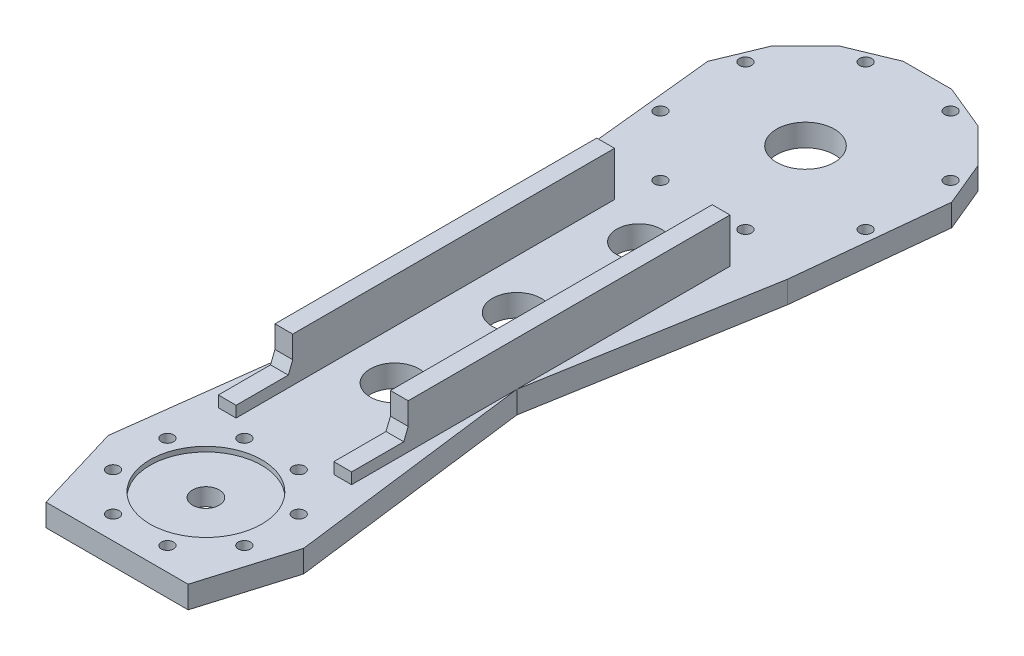
SolidWorks part; units mm, degrees
material "6061-T6 (SS)"
ref_plane "Front Plane" through (0, 0, 0) normal (0, 0, 1) x (1, 0, 0)
ref_plane "Top Plane" through (0, 0, 0) normal (0, 1, 0) x (1, 0, 0)
ref_plane "Right Plane" through (0, 0, 0) normal (1, 0, 0) x (0, 0, -1)
ref_plane "PL_Thigh_Plate_base" through (0, -46, 0) normal (0, 1, 0) x (1, 0, 0)
sketch "SK_Thigh_Plate" plane through (0, -46, 0) normal (0, 1, 0) x (1, 0, 0)
  line L0 (-32, -40) -> (32, -40)
  line L1 (32, -40) -> (44, 0)
  line L2 (44, 0) -> (30, 110)
  line L3 (30, 110) -> (48, 214)
  line L4 (48, 214) -> (54.924, 280.9251)
  line L5 (54.924, 280.9251) -> (46.5623, 301.1119)
  line L6 (46.5623, 301.1119) -> (31.1119, 316.5623)
  line L7 (31.1119, 316.5623) -> (10.9251, 324.924)
  line L8 (10.9251, 324.924) -> (-10.9251, 324.924)
  line L9 (-10.9251, 324.924) -> (-31.1119, 316.5623)
  line L10 (-31.1119, 316.5623) -> (-46.5623, 301.1119)
  line L11 (-46.5623, 301.1119) -> (-54.924, 280.9251)
  line L12 (-54.924, 280.9251) -> (-48, 214)
  line L13 (-48, 214) -> (-30, 110)
  line L14 (-30, 110) -> (-44, 0)
  line L15 (-44, 0) -> (-32, -40)
  circle A0 centre (29.5641, 12.2459) radius 2.75
  circle A1 centre (12.2459, 29.5641) radius 2.75
  circle A2 centre (-12.2459, 29.5641) radius 2.75
  circle A3 centre (-29.5641, 12.2459) radius 2.75
  circle A4 centre (-29.5641, -12.2459) radius 2.75
  circle A5 centre (-12.2459, -29.5641) radius 2.75
  circle A6 centre (12.2459, -29.5641) radius 2.75
  circle A7 centre (29.5641, -12.2459) radius 2.75
  circle A8 centre (46.194, 289.1342) radius 2.75
  circle A9 centre (19.1342, 316.194) radius 2.75
  circle A10 centre (-19.1342, 316.194) radius 2.75
  circle A11 centre (-46.194, 289.1342) radius 2.75
  circle A12 centre (-46.194, 250.8658) radius 2.75
  circle A13 centre (-19.1342, 223.806) radius 2.75
  circle A14 centre (19.1342, 223.806) radius 2.75
  circle A15 centre (46.194, 250.8658) radius 2.75
  circle A16 centre (0, 0) radius 6
  circle A17 centre (0, 270) radius 13
  circle A18 centre (0, 85) radius 11
  circle A19 centre (0, 140) radius 11
  circle A20 centre (0, 195) radius 10
  dimension "D31_SK_Thigh_Plate" = 5.5
  dimension "D34_SK_Thigh_Plate" = 5.5
  dimension "D37_SK_Thigh_Plate" = 5.5
  dimension "D40_SK_Thigh_Plate" = 5.5
  dimension "D43_SK_Thigh_Plate" = 5.5
  dimension "D46_SK_Thigh_Plate" = 5.5
  dimension "D49_SK_Thigh_Plate" = 5.5
  dimension "D52_SK_Thigh_Plate" = 5.5
  dimension "D55_SK_Thigh_Plate" = 5.5
  dimension "D58_SK_Thigh_Plate" = 5.5
  dimension "D61_SK_Thigh_Plate" = 5.5
  dimension "D64_SK_Thigh_Plate" = 5.5
  dimension "D67_SK_Thigh_Plate" = 5.5
  dimension "D70_SK_Thigh_Plate" = 5.5
  dimension "D73_SK_Thigh_Plate" = 5.5
  dimension "D76_SK_Thigh_Plate" = 5.5
  dimension "D79_SK_Thigh_Plate" = 12
  dimension "D80_SK_Thigh_Plate" = 26
  dimension "D82_SK_Thigh_Plate" = 22
  dimension "D84_SK_Thigh_Plate" = 22
  dimension "D86_SK_Thigh_Plate" = 20
  dimension "P1" = 32
  dimension "P2" = 40
  dimension "P3" = 32
  dimension "P4" = 40
  dimension "P5" = 44
  dimension "P6" = 30
  dimension "P7" = 110
  dimension "P8" = 48
  dimension "P9" = 214
  dimension "P10" = 54.924
  dimension "P11" = 280.9251
  dimension "P12" = 46.5623
  dimension "P13" = 301.1119
  dimension "P14" = 31.1119
  dimension "P15" = 316.5623
  dimension "P16" = 10.9251
  dimension "P17" = 324.924
  dimension "P18" = 10.9251
  dimension "P19" = 324.924
  dimension "P20" = 31.1119
  dimension "P21" = 316.5623
  dimension "P22" = 46.5623
  dimension "P23" = 301.1119
  dimension "P24" = 54.924
  dimension "P25" = 280.9251
  dimension "P26" = 48
  dimension "P27" = 214
  dimension "P28" = 30
  dimension "P29" = 110
  dimension "P30" = 44
  dimension "P32" = 29.5641
  dimension "P33" = 12.2459
  dimension "P35" = 12.2459
  dimension "P36" = 29.5641
  dimension "P38" = 12.2459
  dimension "P39" = 29.5641
  dimension "P41" = 29.5641
  dimension "P42" = 12.2459
  dimension "P44" = 29.5641
  dimension "P45" = 12.2459
  dimension "P47" = 12.2459
  dimension "P48" = 29.5641
  dimension "P50" = 12.2459
  dimension "P51" = 29.5641
  dimension "P53" = 29.5641
  dimension "P54" = 12.2459
  dimension "P56" = 46.194
  dimension "P57" = 289.1342
  dimension "P59" = 19.1342
  dimension "P60" = 316.194
  dimension "P62" = 19.1342
  dimension "P63" = 316.194
  dimension "P65" = 46.194
  dimension "P66" = 289.1342
  dimension "P68" = 46.194
  dimension "P69" = 250.8658
  dimension "P71" = 19.1342
  dimension "P72" = 223.806
  dimension "P74" = 19.1342
  dimension "P75" = 223.806
  dimension "P77" = 46.194
  dimension "P78" = 250.8658
  dimension "P81" = 270
  dimension "P83" = 85
  dimension "P85" = 140
  dimension "P87" = 195
extrude "Thigh_Plate" add sketch "SK_Thigh_Plate" along normal blind 10
ref_plane "PL_Pitch_Pilot_Recess_base" through (0, -36, 0) normal (0, 1, 0) x (1, 0, 0)
sketch "SK_Pitch_Pilot_Recess" plane through (0, -36, 0) normal (0, 1, 0) x (1, 0, 0)
  circle A0 centre (0, 0) radius 25.15
  dimension "D1_SK_Pitch_Pilot_Recess" = 50.3
extrude "Pitch_Pilot_Recess" cut sketch "SK_Pitch_Pilot_Recess" against normal blind 2.2
ref_plane "PL_Front_Flange_base" through (22, 0, 0) normal (1, 0, 0) x (0, 0, -1)
sketch "SK_Front_Flange" plane through (22, 0, 0) normal (1, 0, 0) x (0, 0, -1)
  line L0 (35.5977, -31) -> (35.5977, -36)
  line L1 (35.5977, -36) -> (206, -36)
  line L2 (206, -36) -> (206, -16)
  line L3 (206, -16) -> (61.0999, -16)
  line L4 (61.0999, -16) -> (61.0999, -26)
  line L5 (61.0999, -26) -> (59.0999, -31)
  line L6 (59.0999, -31) -> (35.5977, -31)
  dimension "P1" = 35.5977
  dimension "P2" = 31
  dimension "P3" = 35.5977
  dimension "P4" = 36
  dimension "P5" = 206
  dimension "P6" = 36
  dimension "P7" = 206
  dimension "P8" = 16
  dimension "P9" = 61.0999
  dimension "P10" = 16
  dimension "P11" = 61.0999
  dimension "P12" = 26
  dimension "P13" = 59.0999
  dimension "P14" = 31
extrude "Front_Flange" add sketch "SK_Front_Flange" along normal blind 8
ref_plane "PL_Back_Flange_base" through (-30, 0, 0) normal (1, 0, 0) x (0, 0, -1)
sketch "SK_Back_Flange" plane through (-30, 0, 0) normal (1, 0, 0) x (0, 0, -1)
  line L0 (35.5977, -31) -> (35.5977, -36)
  line L1 (35.5977, -36) -> (206, -36)
  line L2 (206, -36) -> (206, -16)
  line L3 (206, -16) -> (61.0999, -16)
  line L4 (61.0999, -16) -> (61.0999, -26)
  line L5 (61.0999, -26) -> (59.0999, -31)
  line L6 (59.0999, -31) -> (35.5977, -31)
  dimension "P1" = 35.5977
  dimension "P2" = 31
  dimension "P3" = 35.5977
  dimension "P4" = 36
  dimension "P5" = 206
  dimension "P6" = 36
  dimension "P7" = 206
  dimension "P8" = 16
  dimension "P9" = 61.0999
  dimension "P10" = 16
  dimension "P11" = 61.0999
  dimension "P12" = 26
  dimension "P13" = 59.0999
  dimension "P14" = 31
extrude "Back_Flange" add sketch "SK_Back_Flange" along normal blind 8
ref_axis "AX_PitchY" through (0, -14.5, 0) along (0, -1, 0)
ref_plane "PL_PitchRef" through (0, 0, 0) normal (-0.6428, 0, 0.766) x (0, -1, 0)
equation "\"Thigh_length\"= 270"
equation "\"Thigh_plate_t\"= 10"
equation "\"Flange_end_z\"= -206"
equation "\"Flange_deep_start_z\"= -61.0999"
equation "\"Flange_shallow_start_z\"= -35.5977"
